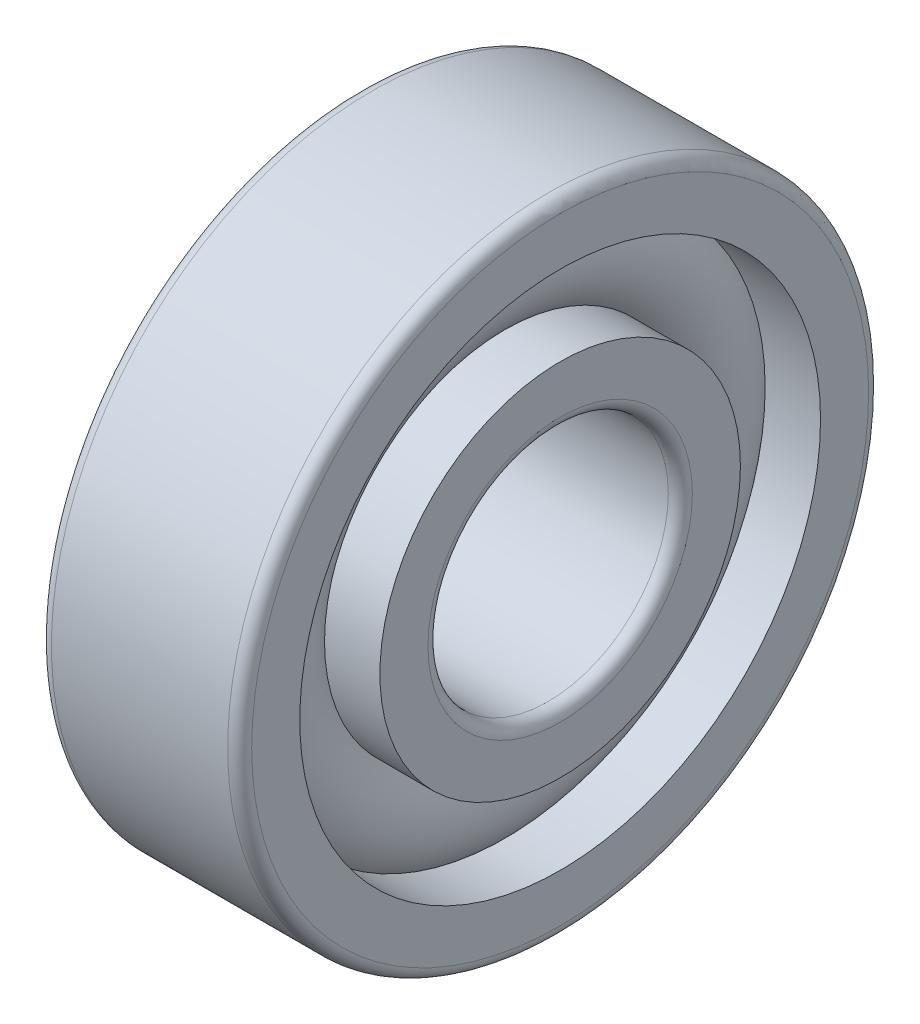
SolidWorks part; units mm, degrees
ref_plane "Plane1" through (0, 0, 0) normal (0, 0, 1) x (1, 0, 0)
ref_plane "Plane2" through (0, 0, 0) normal (0, 1, 0) x (1, 0, 0)
ref_plane "Plane3" through (0, 0, 0) normal (1, 0, 0) x (0, 0, -1)
other "Configuration Table"
sketch "Clipboard" plane through (0, 0, 0) normal (0, 0, 1) x (1, 0, 0)
  line L0 (-10, 0) -> (10, 0) construction
  line L1 (0, 0) -> (22.3471, -0.7804)
  line L2 (0, 0) -> (10.9933, 0.3839)
  line L3 (0, 0) -> (22.3471, -0.7804)
  line L4 (0, 0) -> (-22.3573, -0.3902)
  dimension "BallCLRad" = 11
sketch "CagSpiSke" plane through (0, 0, 0) normal (0, 0, 1) x (1, 0, 0)
  line L0 (0.3, 10.5) -> (0.3, 11.5)
  line L1 (0.3, 11.5) -> (-0.3, 11.5)
  line L2 (-0.3, 11.5) -> (-0.3, 10.5)
  line L3 (-0.3, 10.5) -> (0.3, 10.5)
  line L4 (-20.6375, 0) -> (20.6375, 0) construction
  line L5 (0, 0) -> (0, 23.7692) construction
  dimension "OD" = 23
  dimension "ID" = 21
revolve "CageSpine" add sketch "CagSpiSke" angle 0.001 about L4 reverse direction yes
ref_axis "Axis1" through (-50, 0, 0) along (1, 0, 0)
sketch "CagBalSke" plane through (0, 0, 0) normal (0, 0, 1) x (1, 0, 0)
  line L0 (-3.3, 11) -> (3.3, 11)
  line L1 (-1.905, 11) -> (1.905, 11) construction
  line L2 (-10, 0) -> (10, 0) construction
  line L3 (0, 0) -> (0, 24) construction
  arc A0 (3.3, 11) -> (-3.3, 11) centre (0, 11) cw
  dimension "BallCLRad" = 11
revolve "CageBall" [suppressed] add sketch "CagBalSke" angle 360 about L1 reverse direction yes
pattern_circular "CageBalls" [suppressed] count 2 every 180 about axis through (-50, 0, 0) along (1, 0, 0)
sketch "CagTrmODSke" plane through (0, 0, 0) normal (0, 0, 1) x (1, 0, 0)
  line L0 (3.301, 11.5) -> (3.301, 14.301)
  line L1 (3.301, 14.301) -> (-3.301, 14.301)
  line L2 (-3.301, 14.301) -> (-3.301, 11.5)
  line L3 (-3.301, 11.5) -> (3.301, 11.5)
  line L4 (-20.6375, 0) -> (20.6375, 0) construction
  line L5 (0, 0) -> (0, 25) construction
  dimension "Width" = 6.602
  dimension "ID" = 23
  dimension "OD" = 28.602
revolve "CageTrimOD" [suppressed] cut sketch "CagTrmODSke" angle 360 about L4 reverse direction yes
sketch "CagTrmIDSke" plane through (0, 0, 0) normal (0, 0, 1) x (1, 0, 0)
  line L0 (3.301, 7.701) -> (3.301, 10.5)
  line L1 (3.301, 10.5) -> (-3.301, 10.5)
  line L2 (-3.301, 10.5) -> (-3.301, 7.701)
  line L3 (-3.301, 7.701) -> (3.301, 7.701)
  line L4 (-20.6375, 0) -> (20.6375, 0) construction
  line L5 (0, 0) -> (0, 25) construction
  dimension "Width" = 6.602
  dimension "ID" = 15.402
  dimension "OD" = 21
revolve "CageTrimID" [suppressed] cut sketch "CagTrmIDSke" angle 360 about L4 reverse direction yes
sketch "BalSimSke" plane through (0, 0, 0) normal (0, 0, 1) x (1, 0, 0)
  line L0 (-10, 0) -> (10, 0) construction
  line L1 (-10, 11) -> (10, 11) construction
  line L2 (0, 0) -> (0, 23) construction
  circle A0 centre (0, 11) radius 3
  dimension "BallCLRad" = 11
  dimension "Ball_diameter" = 6
revolve "BallsSimplified" add sketch "BalSimSke" angle 360 about L0
sketch "BalDetSke" plane through (0, 0, 0) normal (0, 0, 1) x (1, 0, 0)
  line L0 (-3, 11) -> (3, 11)
  line L1 (-1.905, 11) -> (1.905, 11) construction
  line L2 (0, 0) -> (0, 25) construction
  arc A0 (3, 11) -> (-3, 11) centre (0, 11) cw
  dimension "BallCLRad" = 11
  dimension "Ball_diameter" = 6
revolve "BallDetailed" [suppressed] add sketch "BalDetSke" angle 360 about L1 reverse direction yes
sketch "InnRacSke" plane through (0, 0, 0) normal (0, 0, 1) x (1, 0, 0)
  line L0 (-2.2024, 9) -> (-5, 9)
  line L1 (-5, 9) -> (-5, 6.6)
  line L2 (-4.4, 6) -> (4.4, 6)
  line L3 (5, 6.6) -> (5, 9)
  line L4 (5, 9) -> (2.2024, 9)
  line L5 (-20.6375, 0) -> (20.6375, 0) construction
  line L6 (0, 0) -> (0, 30) construction
  arc A0 (-5, 6.6) -> (-4.4, 6) centre (-4.4, 6.6) ccw
  arc A1 (4.4, 6) -> (5, 6.6) centre (4.4, 6.6) ccw
  arc A2 (2.2024, 9) -> (-2.2024, 9) centre (0, 11) cw
  dimension "BallCLRad" = 11
  dimension "Fillet_radius" = 0.6
  dimension "Ball_diameter" = 5.95
  dimension "ID" = 12
  dimension "OD" = 18
  dimension "Width" = 10
revolve "InnerRace" add sketch "InnRacSke" angle 360 about L5 reverse direction yes
sketch "OutRacSke" plane through (0, 0, 0) normal (0, 0, 1) x (1, 0, 0)
  line L0 (-2.2024, 13) -> (-5, 13)
  line L1 (-5, 13) -> (-5, 15.4)
  line L2 (-4.4, 16) -> (4.4, 16)
  line L3 (5, 15.4) -> (5, 13)
  line L4 (5, 13) -> (2.2024, 13)
  line L5 (-20.6375, 0) -> (20.6375, 0) construction
  line L6 (0, 0) -> (0, 30) construction
  arc A0 (-5, 15.4) -> (-4.4, 16) centre (-4.4, 15.4) cw
  arc A1 (4.4, 16) -> (5, 15.4) centre (4.4, 15.4) cw
  arc A2 (2.2024, 13) -> (-2.2024, 13) centre (0, 11) ccw
  dimension "BallCLRad" = 11
  dimension "Fillet_radius" = 0.6
  dimension "Ball_diameter" = 5.95
  dimension "Width" = 10
revolve "OuterRace" add sketch "OutRacSke" angle 360 about L5 reverse direction yes
pattern_circular "BallsDetailed" [suppressed] count 2 every 180 about axis through (-50, 0, 0) along (1, 0, 0)
equation "\"BallCLRad@Clipboard\" = ( \"OD@OutRacSke\" + \"ID@InnRacSke\" ) / 4"
equation "\"BallCLRad@BalSimSke\" = \"BallCLRad@Clipboard\""
equation "\"BallCLRad@BalDetSke\" = \"BallCLRad@Clipboard\""
equation "\"BallCLRad@InnRacSke\" = \"BallCLRad@Clipboard\""
equation "\"BallCLRad@OutRacSke\" = \"BallCLRad@Clipboard\""
equation "\"Ball_diameter@InnRacSke\" = \"Ball_diameter@BalDetSke\" - 0.05"
equation "\"Ball_diameter@OutRacSke\" = \"Ball_diameter@BalDetSke\" - 0.05"
equation "\"Ball_diameter@BalSimSke\" = \"Ball_diameter@BalDetSke\""
equation "\"Width@OutRacSke\" = \"Width@InnRacSke\""
equation "\"Fillet_radius@OutRacSke\" = \"Fillet_radius@InnRacSke\""
equation "\"Max_count@Clipboard\" = int( 3.14159265 / atn(( \"Ball_diameter@BalDetSke\" / 2) / sqr( \"BallCLRad@Clipboard\"  *  \"BallCLRad@Clipboard\" - ( \"Ball_diameter@BalDetSke\" / 2) *  ( \"Ball_diameter@BalDetSke\" / 2))))"
equation "\"Max_count@Clipboard\" = ((sgn( \"Max_count@Clipboard\" - \"Count@Clipboard\" )-1)*( \"Max_count@Clipboard\" - \"Count@Clipboard\" ))/-2+ \"Count@Clipboard\""
equation "\"Count@BallsDetailed\" = int( \"Show_count@Clipboard\" ) "
equation "\"Count@BallsDetailed\" = ((sgn( \"Count@BallsDetailed\" - \"Max_count@Clipboard\" )-1)*( \"Count@BallsDetailed\" - \"Max_count@Clipboard\" ))/-2+ \"Max_count@Clipboard\""
equation "\"Count@BallsDetailed\" = ((sgn( \"Count@BallsDetailed\" - \"Min_count@Clipboard\" )+1)*( \"Count@BallsDetailed\" - \"Min_count@Clipboard\"))/2 +\"Min_count@Clipboard\""
equation "\"Angle@BallsDetailed\" = 360.0 / \"Max_count@Clipboard\""
equation "\"BallCLRad@CagBalSke\" = \"BallCLRad@Clipboard\""
equation "\"Count@CageBalls\" = \"Count@BallsDetailed\""
equation "\"Angle@CageBalls\" = \"Angle@BallsDetailed\""
equation "\"Angle@CageSpine\" =  \"Angle@CageBalls\" * ( \"Count@CageBalls\" -1 + int( \"Count@CageBalls\" / \"Max_count@Clipboard\" ) )  + 0.001 -  int( \"Count@CageBalls\" / \"Max_count@Clipboard\" ) * 0.001"
equation "\"Angle@CageSpine\" =  \"Angle@CageSpine\" * int( \"Min_count@Clipboard\" / 2) + int(1 / \"Min_count@Clipboard\")  * 0.001"
equation "\"CageWallOD@CagBalSke\" =  \"Ball_diameter@BalDetSke\" * 1.1"
equation "\"Thickness@CagSpiSke\" =  \"Ball_diameter@BalDetSke\" * 0.1"
equation "\"OD@CagTrmODSke\" = \"BallCLRad@Clipboard\" * 2 + \"CageWallOD@CagBalSke\" + 0.002"
equation "\"ID@CagTrmODSke\" = \"BallCLRad@Clipboard\" * 2 + \"Ball_diameter@BalDetSke\" / 6"
equation "\"OD@CagTrmIDSke\" = \"BallCLRad@Clipboard\" * 2 - \"Ball_diameter@BalDetSke\" / 6"
equation "\"ID@CagTrmIDSke\" = \"BallCLRad@Clipboard\" * 2 - \"CageWallOD@CagBalSke\" + 0.002"
equation "\"OD@CagSpiSke\" = \"ID@CagTrmODSke\""
equation "\"ID@CagSpiSke\" = \"OD@CagTrmIDSke\""
equation "\"Width@CagTrmODSke\" = \"CageWallOD@CagBalSke\" + 0.002"
equation "\"Width@CagTrmIDSke\" = \"CageWallOD@CagBalSke\" + 0.002"
